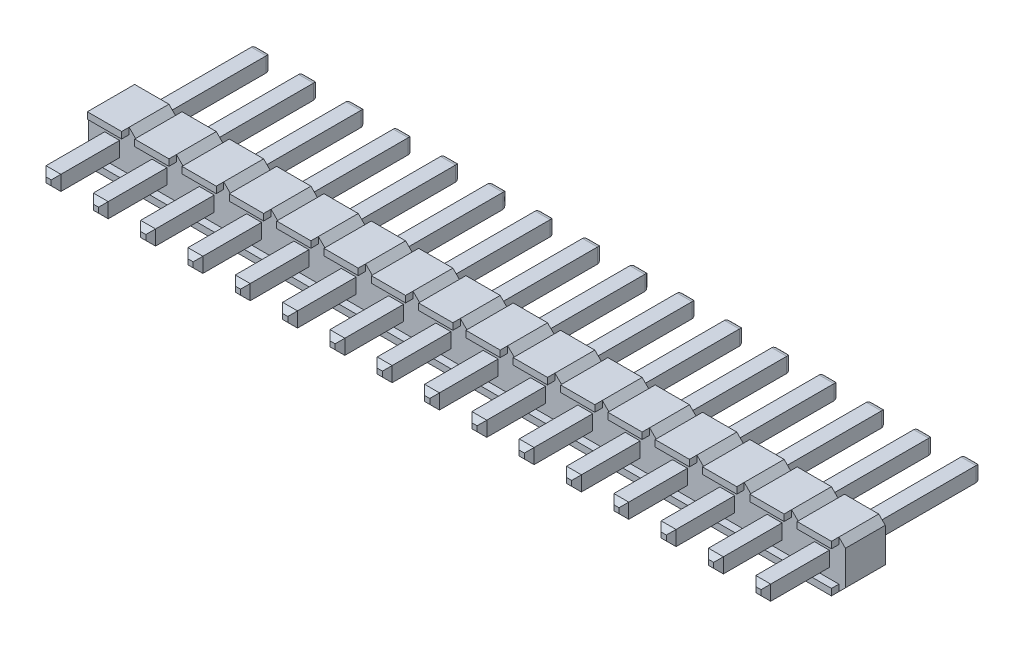
SolidWorks part; units mm, degrees
ref_plane "Front Plane" through (0, 0, 0) normal (0, 0, 1) x (1, 0, 0)
ref_plane "Top Plane" through (0, 0, 0) normal (0, 1, 0) x (1, 0, 0)
ref_plane "Right Plane" through (0, 0, 0) normal (1, 0, 0) x (0, 0, -1)
sketch "Sketch1" plane through (0, 0, 0) normal (0, 0, 1) x (1, 0, 0)
  line L0 (1.27, 0.92) -> (0.92, 1.27)
  line L1 (0.92, 1.27) -> (-0.92, 1.27)
  line L2 (-0.92, 1.27) -> (-1.27, 0.92)
  line L3 (-1.27, 0.92) -> (-1.27, -0.92)
  line L4 (-1.27, -0.92) -> (-0.92, -1.27)
  line L5 (-0.92, -1.27) -> (0.92, -1.27)
  line L6 (0.92, -1.27) -> (1.27, -0.92)
  line L7 (1.27, 0.92) -> (1.27, -0.92)
  line L8 (-0.3938, -0.3997) -> (-0.3938, 0.4003)
  line L9 (0.4062, -0.3997) -> (-0.3938, -0.3997)
  line L10 (0.4062, 0.4003) -> (0.4062, -0.3997)
  line L11 (-0.3938, 0.4003) -> (0.4062, 0.4003)
extrude "Boss-Extrude1" add sketch "Sketch1" along normal blind 2.14
sketch "Sketch4" plane through (0, 0, 2.14) normal (0, 0, 1) x (1, 0, 0)
  line L0 (-0.92, 1.27) -> (-0.92, 0.92)
  line L1 (0.92, 1.27) -> (0.92, 0.92)
  line L3 (-0.92, -0.92) -> (-0.92, -1.27)
  line L4 (-0.92, -0.92) -> (0.92, -0.92)
  line L5 (0.92, -0.92) -> (0.92, -1.27)
  line L6 (0.92, 0.92) -> (-0.92, 0.92)
  line L15 (1.27, -0.92) -> (1.27, 0.92)
  line L16 (1.27, 0.92) -> (0.92, 1.27)
  line L17 (0.92, 1.27) -> (-0.92, 1.27)
  line L18 (-0.92, 1.27) -> (-1.27, 0.92)
  line L19 (-1.27, 0.92) -> (-1.27, -0.92)
  line L20 (-1.27, -0.92) -> (-0.92, -1.27)
  line L21 (-0.92, -1.27) -> (0.92, -1.27)
  line L22 (0.92, -1.27) -> (1.27, -0.92)
  line L25 (0.92, 1.27) -> (-0.92, 1.27)
  line L29 (-0.92, -1.27) -> (0.92, -1.27)
  dimension "D1" = 0
extrude "Boss-Extrude2" add sketch "Sketch4" along normal blind 0.4
ref_plane "Plane1" through (0, 0, -6) normal (0, 0, -1) x (-1, 0, 0)
sketch "Sketch12" plane through (0, 0, -6) normal (0, 0, -1) x (-1, 0, 0)
  line L0 (0, 0.3915) -> (0, -0.4085) construction
  line L3 (-0.4, -0.4085) -> (0.4, -0.4085)
  line L4 (-0.4, -0.4085) -> (-0.4, 0.3915)
  line L5 (-0.4, 0.3915) -> (0.4, 0.3915)
  line L6 (0.4, -0.4085) -> (0.4, 0.3915)
  line L7 (-0.4, -0.4085) -> (0.4, 0.3915) construction
  line L8 (-0.4, 0.3915) -> (0.4, -0.4085) construction
  point P5 (0, -0.0085)
extrude "Boss-Extrude3" add sketch "Sketch12" against normal blind 11.54
fillet "Fillet1" radius 0.26 4 edges at (0, 0.3915, 5.54) (0.4, -0.0085, 5.54) (0, -0.4085, 5.54) (-0.4, -0.0085, 5.54) profile chamfer
fillet "Fillet2" radius 0.26 4 edges at (0, -0.4085, -6) (0.4, -0.0085, -6) (0, 0.3915, -6) (-0.4, -0.0085, -6)
pattern_linear "LPattern9" count 16 spacing 2.54 along (1, 0, 0) of "Boss-Extrude3", "Boss-Extrude1", "Boss-Extrude2", "Fillet1", "Fillet2"
